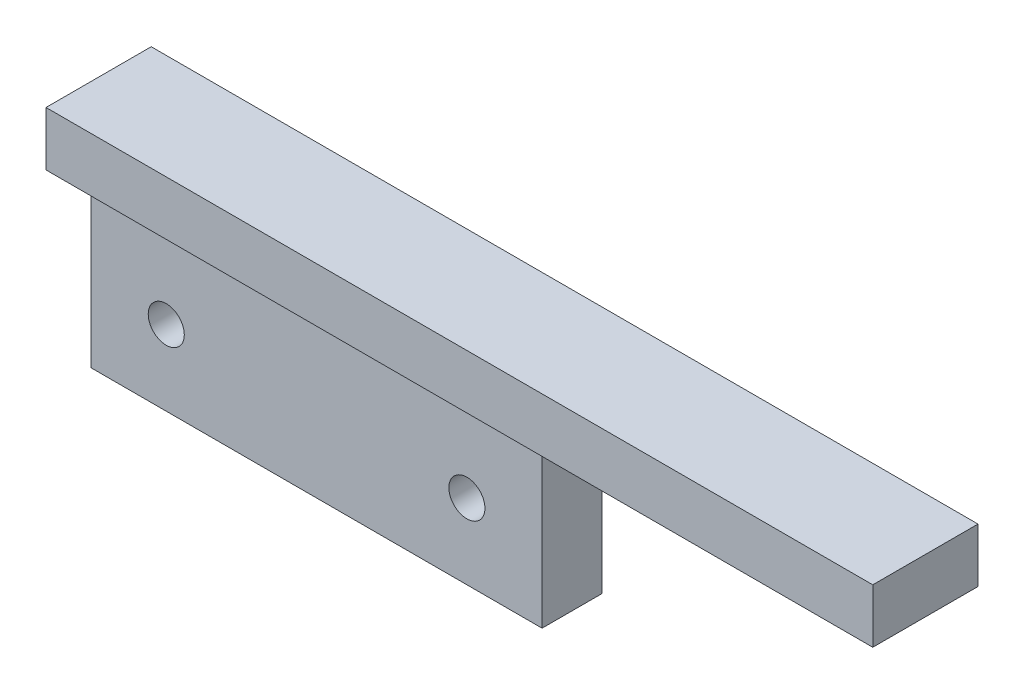
SolidWorks part; units mm, degrees
ref_plane "정면" through (0, 0, 0) normal (0, 0, 1) x (1, 0, 0)
ref_plane "윗면" through (0, 0, 0) normal (0, 1, 0) x (1, 0, 0)
ref_plane "우측면" through (0, 0, 0) normal (1, 0, 0) x (0, 0, -1)
sketch "스케치1" plane through (0, 0, 0) normal (0, 0, 1) x (1, 0, 0)
  line L1 (-30, 12.5) -> (30, 12.5)
  line L2 (-30, 12.5) -> (-30, -12.5)
  line L3 (-30, -12.5) -> (30, -12.5)
  line L4 (30, 12.5) -> (30, -12.5)
  line L5 (-30, 12.5) -> (30, -12.5) construction
  line L6 (-30, -12.5) -> (30, 12.5) construction
  point P0 (0, 0)
  dimension "D1" = 25
  dimension "D2" = 60
extrude "보스-돌출1" add sketch "스케치1" along normal blind 8
sketch "스케치2" plane through (0, 0, 8) normal (0, 0, 1) x (1, 0, 0)
  line L0 (30, -12.5) -> (30, 12.5) construction
  line L1 (-30, 12.5) -> (30, 12.5)
  line L2 (-30, 12.5) -> (-30, 20.5)
  line L3 (-30, 20.5) -> (30, 20.5)
  line L4 (30, 12.5) -> (30, 20.5)
  dimension "D1" = 8
extrude "보스-돌출2" add sketch "스케치2" against normal up to vertex (8 mm away) and the other way blind 6 up to point (30, 12.5, 0)
sketch "스케치3" plane through (30, 0, 0) normal (1, 0, 0) x (0, 0, -1)
  line L0 (-14, 12.5) -> (-14, 20.5) construction
  line L1 (-8, 12.5) -> (-14, 12.5)
  line L2 (-8, 12.5) -> (-8, 13.3)
  line L3 (-8, 13.3) -> (-14, 13.3)
  line L4 (-14, 12.5) -> (-14, 13.3)
  dimension "D1" = 0.8
extrude "컷-돌출1" cut sketch "스케치3" against normal through all both and the other way through all
hole_wizard "M4 소켓 머리 캡 나사용 카운터보어1" positions "스케치5" profile "스케치6" counterbore size "M4" standard "KS"
sketch "스케치5" plane through (0, 0, 0) normal (0, 0, -1) x (-1, 0, 0)
  line L0 (30, -12.5) -> (-30, -12.5) construction
  line L1 (30, 20.5) -> (30, -12.5) construction
  line L2 (-30, -12.5) -> (-30, 20.5) construction
  point P0 (-20, -2.5)
  point P2 (20, -2.5)
  dimension "D1" = 10
  dimension "D2" = 10
  dimension "D3" = 10
  dimension "D4" = 10
sketch "스케치6" plane through (20, -2.5, 0) normal (1, 0, 0) x (0, 1, 0)
  line L0 (0, 0) -> (0, 11.5421)
  line L1 (0, 11.5421) -> (2.4, 10.1)
  line L2 (2.4, 10.1) -> (2.4, 4)
  line L3 (2.4, 4) -> (4, 4)
  line L4 (4, 4) -> (4, 0)
  line L5 (4, 0) -> (0, 0)
  line L10 (0, 11.5421) -> (-2.4, 10.1) construction
  line L11 (0, -6.35) -> (0, 107.95) construction
  dimension "구멍 지름" = 4.8
  dimension "구멍 깊이" = 10.1
  dimension "카운터보어 지름" = 8
  dimension "카운터보어 깊이" = 4
  dimension "드릴 각도" = 118
sketch "스케치7" plane through (30, 0, 0) normal (-1, 0, 0) x (0, 0, 1)
  line L1 (0, 20.5) -> (14, 20.5)
  line L2 (0, 20.5) -> (0, 13.3)
  line L3 (0, 13.3) -> (14, 13.3)
  line L4 (14, 20.5) -> (14, 13.3)
extrude "보스-돌출3" add sketch "스케치7" against normal blind 50
